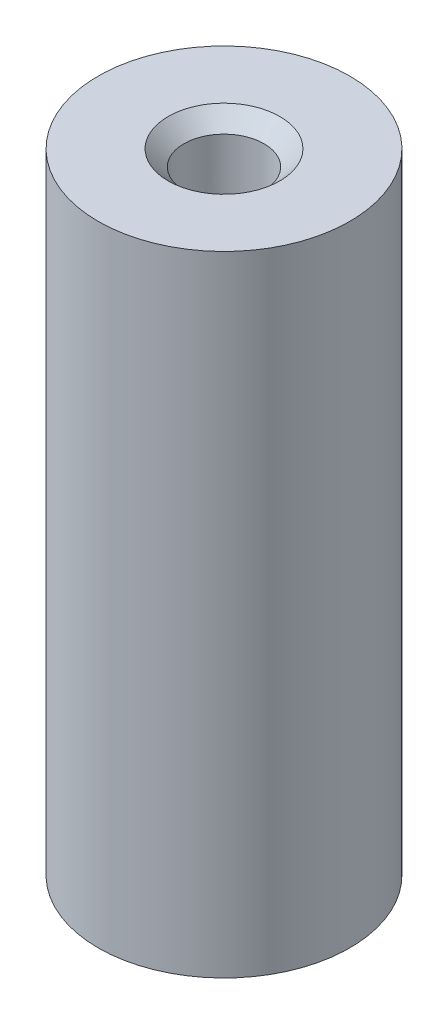
SolidWorks part; units mm, degrees
material "ABS"
ref_plane "Front Plane" through (0, 0, 0) normal (0, 0, 1) x (1, 0, 0)
ref_plane "Top Plane" through (0, 0, 0) normal (0, 1, 0) x (1, 0, 0)
ref_plane "Right Plane" through (0, 0, 0) normal (1, 0, 0) x (0, 0, -1)
sketch "Sketch1" plane through (0, 0, 0) normal (0, 1, 0) x (1, 0, 0)
  circle A0 centre (0, 0) radius 4
  dimension "D1" = 8
extrude "Boss-Extrude1" add sketch "Sketch1" along normal blind 20
sketch "Sketch2" plane through (0, 0, 0) normal (0, -1, 0) x (1, 0, 0)
  circle A0 centre (0, 0) radius 2.45
  dimension "D1" = 4.9
extrude "Cut-Extrude1" cut sketch "Sketch2" against normal blind 6
sketch "Sketch3" plane through (0, 6, 0) normal (0, -1, 0) x (1, 0, 0)
  circle A0 centre (0, 0) radius 2.7
  dimension "D1" = 5.4
extrude "Cut-Extrude2" cut sketch "Sketch3" against normal blind 10
sketch "Sketch4" plane through (0, 16, 0) normal (0, -1, 0) x (1, 0, 0)
  circle A0 centre (0, 0) radius 1.275
  dimension "D1" = 2.55
extrude "Cut-Extrude3" cut sketch "Sketch4" against normal blind 6
chamfer "Chamfer1" distance 0.5 angle 45 3 edges at (0, 0, -2.45) (0, 6, -2.45) (0, 20, 1.275)
chamfer "Chamfer2" distance 1.5 angle 45 1 edges at (0, 16, -1.275)
